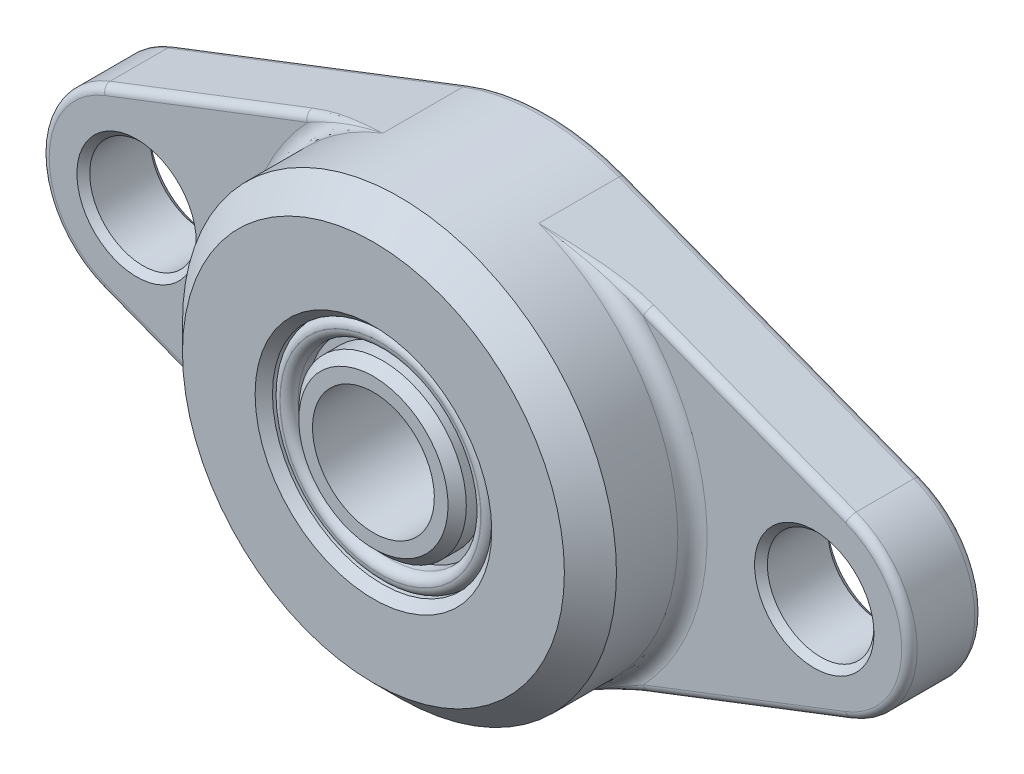
SolidWorks part; units mm, degrees
ref_plane "Front Plane" through (0, 0, 0) normal (0, 0, 1) x (1, 0, 0)
ref_plane "Top Plane" through (0, 0, 0) normal (0, 1, 0) x (1, 0, 0)
ref_plane "Right Plane" through (0, 0, 0) normal (1, 0, 0) x (0, 0, -1)
sketch "Sketch1" plane through (0, 0, 0) normal (0, 0, 1) x (1, 0, 0)
  line L0 (0, -14.25) -> (0, 14.25) construction
  line L1 (-28.5, 0) -> (28.5, 0) construction
  line L2 (-22.25, 0) -> (22.25, 0) construction
  line L3 (22.25, -3.5) -> (22.25, 3.5) construction
  line L4 (-4, 0) -> (4, 0) construction
  point P4 (0, 0)
  point P8 (0, 0)
  point P11 (0, 0)
  point P14 (22.25, 0)
  point P17 (0, 0)
  dimension "ID" = 8
  dimension "Overall Height" = 28.5
  dimension "Overall Length" = 57
  dimension "Mounting Hole Center to Center" = 44.5
  dimension "Mounting Hole Diameter" = 7
sketch "Sketch2" plane through (0, 0, 0) normal (1, 0, 0) x (0, 0, -1)
  line L0 (-5.75, 0) -> (5.75, 0) construction
  point P0 (0.95, 0)
  point P4 (0, 0)
  dimension "Overall Width" = 11.5
  dimension "Flange Thickness" = 4.8
sketch "Sketch3" plane through (0, 0, 0) normal (0, 0, 1) x (1, 0, 0)
  line L0 (0, -14.25) -> (0, 14.25) construction
  line L1 (-24.4972, 5.832) -> (-5.1236, 13.297)
  line L2 (-24.4972, -5.832) -> (-5.1236, -13.297)
  line L3 (5.1236, -13.297) -> (24.4972, -5.832)
  line L4 (5.1236, 13.297) -> (24.4972, 5.832)
  circle A0 centre (22.25, 0) radius 6.25 construction
  circle A1 centre (-22.25, 0) radius 6.25 construction
  circle A2 centre (0, 0) radius 14.25 construction
  circle A3 centre (22.25, 0) radius 3.5
  circle A4 centre (-22.25, 0) radius 3.5
  arc A5 (-24.4972, 5.832) -> (-24.4972, -5.832) centre (-22.25, 0) ccw
  arc A6 (24.4972, 5.832) -> (24.4972, -5.832) centre (22.25, 0) cw
  arc A7 (-5.1236, 13.297) -> (5.1236, 13.297) centre (0, 0) cw
  arc A8 (-5.1236, -13.297) -> (5.1236, -13.297) centre (0, 0) ccw
extrude "Boss-Extrude1" add sketch "Sketch3" along normal up to vertex (-0.95 mm away) from vertex up to point (0, 0, -0.95) starting at point (0, 0, -5.75)
sketch "Sketch4" plane through (0, 0, -0.95) normal (0, 0, 1) x (1, 0, 0)
  line L0 (0, -14.25) -> (0, 14.25) construction
  circle A0 centre (0, 0) radius 14.25
extrude "Boss-Extrude2" add sketch "Sketch4" along normal up to vertex (6.7 mm away) up to point (0, 0, 5.75)
fillet "Fillet1" radius 0.96 2 edges at (-14.25, 0, -0.95) (14.25, 0, -0.95)
chamfer "Chamfer1" distance 1.71 angle 45 1 edges at (14.25, 0, 5.75)
chamfer "Chamfer2" distance 0.42 angle 45 4 edges at (-18.75, 0, -0.95) (25.75, 0, -0.95) (25.75, 0, -5.75) (-18.75, 0, -5.75)
fillet "Fillet2" radius 0.508 18 edges at (-8.2944, 12.0753, -0.7694) (-8.2944, -12.0753, -0.7694) (-17.2916, -8.6085, -0.95) (-28.5, 0, -0.95) (8.2944, -12.0753, -0.7694) (17.2916, -8.6085, -0.95) (28.5, 0, -0.95) (8.2944, 12.0753, -0.7694) (-17.2916, 8.6085, -0.95) (17.2916, 8.6085, -0.95) (-28.5, 0, -5.75) (-14.8104, 9.5645, -5.75) (0, 14.25, -5.75) (14.8104, 9.5645, -5.75) (28.5, 0, -5.75) (14.8104, -9.5645, -5.75) (0, -14.25, -5.75) (-14.8104, -9.5645, -5.75)
sketch "Sketch5" plane through (0, 0, 5.75) normal (0, 0, 1) x (1, 0, 0)
  circle A0 centre (0, 0) radius 7.2
  dimension "Housing ID" = 14.4
extrude "Cut-Extrude1" cut sketch "Sketch5" against normal through all
sketch "Sketch6" plane through (0, 0, -5.75) normal (0, 0, -1) x (-1, 0, 0)
  line L0 (0, -14.25) -> (0, 14.25) construction
  line L1 (0, 8) -> (0.8504, 7.1496)
  line L2 (0, 8) -> (-0.8504, 7.1496)
  line L3 (-0.8504, 7.1496) -> (0.8504, 7.1496)
  line L4 (0, 7.1496) -> (0, 8) construction
  circle A0 centre (0, 0) radius 8 construction
  circle A1 centre (0, 0) radius 7.2 construction
  circle A3 centre (0, 0) radius 7.2 construction
  dimension "Star Pattern OD" = 16
  dimension "D2" = 90
extrude "Cut-Extrude2" cut sketch "Sketch6" against normal blind 9.2
pattern_circular "CirPattern1" count 40 over 360 about axis through (0, 0, 5.75) along (0, 0, -1) of "Cut-Extrude2" reverse direction yes
chamfer "Chamfer3" distance 0.57 angle 45 1 edges at (7.2, 0, 5.75)
sketch "Sketch8" plane through (0, 0, -5.75) normal (0, 0, -1) x (-1, 0, 0)
  circle A0 centre (0, 0) radius 7.2
  circle A1 centre (0, 0) radius 6
  circle A2 centre (0, 0) radius 7.2 construction
  dimension "Black Bushing ID" = 12
extrude "Boss-Extrude3" add sketch "Sketch8" against normal blind 11.04 separate body
sketch "Sketch9" plane through (0, 0, -5.75) normal (0, 0, -1) x (-1, 0, 0)
  line L0 (0, 8) -> (-0.8504, 7.1496)
  line L1 (-0.8504, 7.1496) -> (0.8504, 7.1496)
  line L2 (0.8504, 7.1496) -> (0, 8)
extrude "Boss-Extrude4" add sketch "Sketch9" against normal blind 9.2
pattern_circular "CirPattern5" count 40 over 360 about axis through (0, 0, 5.75) along (0, 0, -1) of "Boss-Extrude4" reverse direction yes
fillet "Fillet3" radius 0.588 2 edges at (-6, 0, 5.29) (-7.2, 0, 5.29)
sketch "Sketch10" plane through (0, 0, 0) normal (1, 0, 0) x (0, 0, -1)
  line L0 (-5.75, 0) -> (5.75, 0) construction
  line L1 (-5.75, 12.54) -> (-5.75, -12.54) construction
  line L2 (0, 4) -> (0, -4) construction
  line L3 (0, -14.25) -> (0, 14.25) construction
  line L4 (-5.75, 4) -> (5.75, 4)
  line L5 (0, -6.6) -> (0, 6.6) construction
  line L6 (-5.75, 4) -> (-5.75, 5.5)
  line L8 (5.75, 5.5) -> (5.75, 4)
  line L9 (0, -5.5) -> (0, 5.5) construction
  line L10 (0, 5.5) -> (-5.75, 5.5) construction
  line L11 (-4.025, 6.6) -> (4.025, 6.6)
  line L12 (-5.75, 5.5) -> (-4.025, 5.5)
  line L13 (-4.025, 5.5) -> (-4.025, 6.6)
  line L14 (5.75, 5.5) -> (0, 5.5) construction
  line L15 (4.025, 6.6) -> (4.025, 5.5)
  line L16 (4.025, 5.5) -> (5.75, 5.5)
  point P11 (0, 0)
  point P15 (0, 4)
  point P18 (0, 0)
  point P24 (0, 0)
  point P27 (0, 6.6)
  dimension "D1" = 8
  dimension "D2" = 11.5
  dimension "D3" = 13.2
  dimension "White Bushing OD" = 11
  dimension "D4" = 8.05
revolve "Revolve1" add sketch "Sketch10" angle 360 about L0
sketch "Sketch11" plane through (0, 0, 0) normal (1, 0, 0) x (0, 0, -1)
  line L0 (-4.025, 6.6) -> (4.025, 6.6)
  line L1 (4.025, 6.6) -> (4.025, 5.5)
  line L2 (4.025, 5.5) -> (-4.025, 5.5)
  line L3 (-4.025, 5.5) -> (-4.025, 6.6)
  line L4 (-5.75, 0) -> (5.75, 0) construction
revolve "Cut-Revolve1" cut sketch "Sketch11" angle 360 about L4
fillet "Fillet4" radius 0.254 1 edges at (-6, 0, -5.75)
chamfer "Chamfer4" distance 0.6 angle 45 2 edges at (0, -5.5, -5.75) (0, -5.5, 5.75)
sketch "Sketch12" plane through (0, 0, 0) normal (0, 0, 1) x (1, 0, 0)
  line L0 (-22.25, 0) -> (22.25, 0) construction
  line L2 (-28.5, 0) -> (28.5, 0) construction
  line L3 (-18.75, 0) -> (-25.75, 0)
  point P4 (0, 0)
  point P5 (0, 0)
  point P8 (-22.25, 0)
  point P10 (0, 0)
  point P11 (0, 0)
  point P12 (22.25, 0)
  point P18 (0, 0)
  point P19 (-28.5, 0)
  point P20 (28.5, 0)
  point P23 (-22.25, 0)
  point P24 (-25.75, 0)
  point P25 (-18.75, 0)
  dimension "D1" = 44.5
  dimension "D2" = 57
  dimension "D3" = 7
sketch "Sketch13" plane through (0, 0, 0) normal (1, 0, 0) x (0, 0, -1)
  line L0 (5.75, -14.25) -> (5.75, 14.25) construction
  line L1 (5.75, -14.25) -> (0.95, -14.25) construction
  point P0 (-5.75, 12.54)
  point P4 (5.75, 0)
  point P7 (0.95, -14.25)
  point P8 (5.75, -14.25)
  point P9 (5.75, 14.25)
  dimension "D1" = 28.5
  dimension "D2" = 4.8
equation "\"D1@Cut-Extrude2\"=\"Overall Width@sketch2\"*.8"
equation "\"D1@Fillet1\" = \"Flange Thickness@Sketch2\" * .2"
equation "\"D1@Chamfer1\" = \"Overall Height@Sketch1\" * .06"
equation "\"D1@Chamfer2\" = \"Mounting Hole Diameter@Sketch1\" * .06"
equation "\"D1@Chamfer3\"=\"Overall Height@sketch1\"*.02"
equation "\"D1@Boss-Extrude4\"=\"D1@Cut-Extrude2\""
equation "\"D1@CirPattern5\"=\"D1@CirPattern1\""
equation "\"D1@Fillet3\"=( \"Housing ID@Sketch5\" - \"Black Bushing ID@Sketch8\" )  *.245"
equation "\"D1@Sketch10\"=\"ID@sketch1\""
equation "\"D2@Sketch10\"=\"Overall Width@sketch2\""
equation "\"D3@Sketch10\" = \"Black Bushing ID@Sketch8\" * 1.1"
equation "\"D4@Sketch10\"=\"D2@Sketch10\"*.7"
equation "\"D1@Fillet5\" = \"White Bushing OD@Sketch10\" * .04"
equation "\"D1@Chamfer4\" =  (  ( \"White Bushing OD@Sketch10\" - \"ID@Sketch1\" )  / 2 )  * .4"
equation "\"D1@Sketch12\"=\"Mounting Hole Center to Center@sketch1\""
equation "\"D2@Sketch12\"=\"Overall length@sketch1\""
equation "\"D3@Sketch12\"=\"Mounting Hole Diameter@sketch1\""
equation "\"D1@Sketch13\"=\"Overall Height@sketch1\""
equation "\"D2@Sketch13\"=\"Flange Thickness@sketch2\""
equation "\"D1@Boss-Extrude3\"=\"Overall Width@Sketch2\" * .96"
